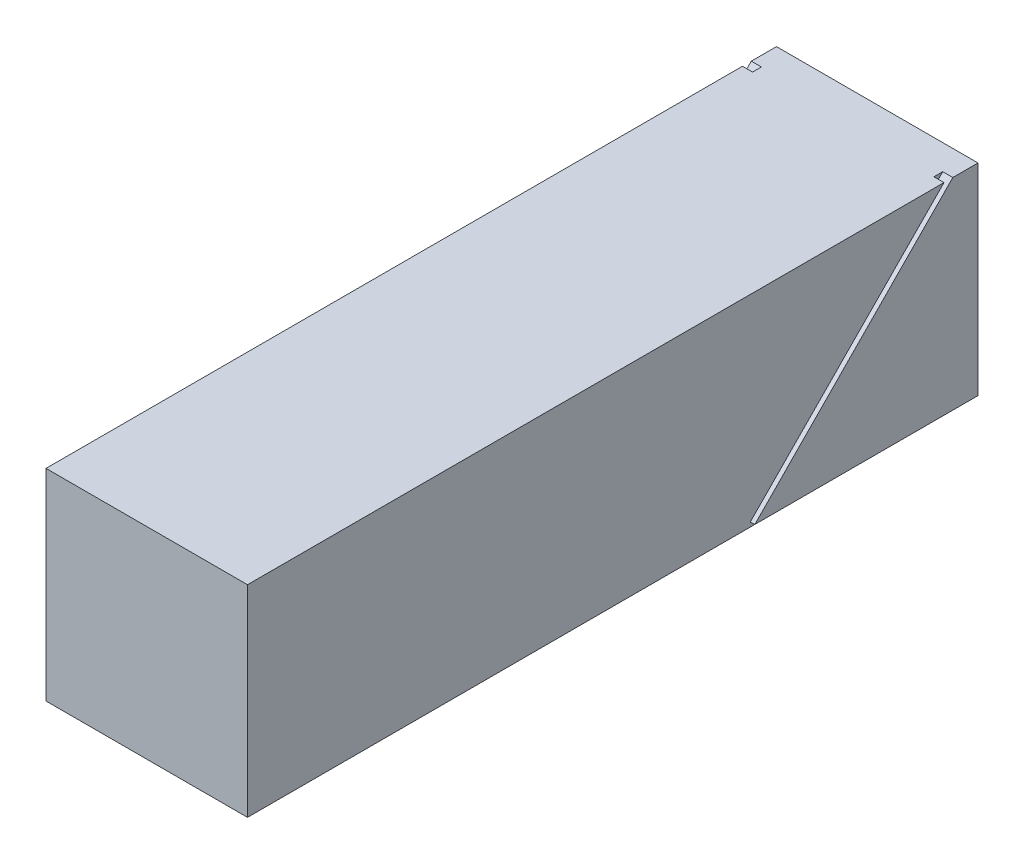
SolidWorks part; units mm, degrees
ref_plane "Front Plane" through (0, 0, 0) normal (0, 0, 1) x (1, 0, 0)
ref_plane "Top Plane" through (0, 0, 0) normal (0, 1, 0) x (1, 0, 0)
ref_plane "Right Plane" through (0, 0, 0) normal (1, 0, 0) x (0, 0, -1)
sketch "Sketch1" plane through (0, 0, 0) normal (0, 0, 1) x (1, 0, 0)
  line L1 (0, 0) -> (50.8, 0)
  line L2 (0, 0) -> (0, 50.8)
  line L3 (0, 50.8) -> (50.8, 50.8)
  line L4 (50.8, 0) -> (50.8, 50.8)
  dimension "D1" = 50.8
extrude "Boss-Extrude1" add sketch "Sketch1" along normal blind 184.15
sketch "Sketch2" plane through (50.8, 0, 0) normal (1, 0, 0) x (0, 0, -1)
  line L0 (-56.271, 0) -> (-6.35, 50.8)
  line L1 (-184.15, 0) -> (0, 0) construction
  line L2 (-184.15, 50.8) -> (0, 50.8) construction
  line L3 (0, 0) -> (0, 50.8) construction
  line L4 (-57.4033, 1.1127) -> (-8.5757, 50.8)
  line L5 (-8.5757, 50.8) -> (-6.35, 50.8)
  line L7 (-56.5295, 0.254) -> (-57.4033, 1.1127)
  line L8 (-56.5295, 0.254) -> (-56.5295, 0)
  line L9 (-56.5295, 0) -> (-56.271, 0)
  line L10 (-56.5295, 0.254) -> (-56.271, 0) construction
  dimension "D1" = 45.5
  dimension "D2" = 6.35
  dimension "D3" = 1.5875
  dimension "D4" = 0.254
extrude "Cut-Extrude1" cut sketch "Sketch2" against normal blind 2.54
extrude "Cut-Extrude2" cut sketch "Sketch2<2>" along normal blind 2.54 from surface starting at face at (0, 25.4, 92.075)
sketch "Sketch2<2>" plane through (50.8, 0, 0) normal (1, 0, 0) x (0, 0, -1) same geometry as "Sketch2"
